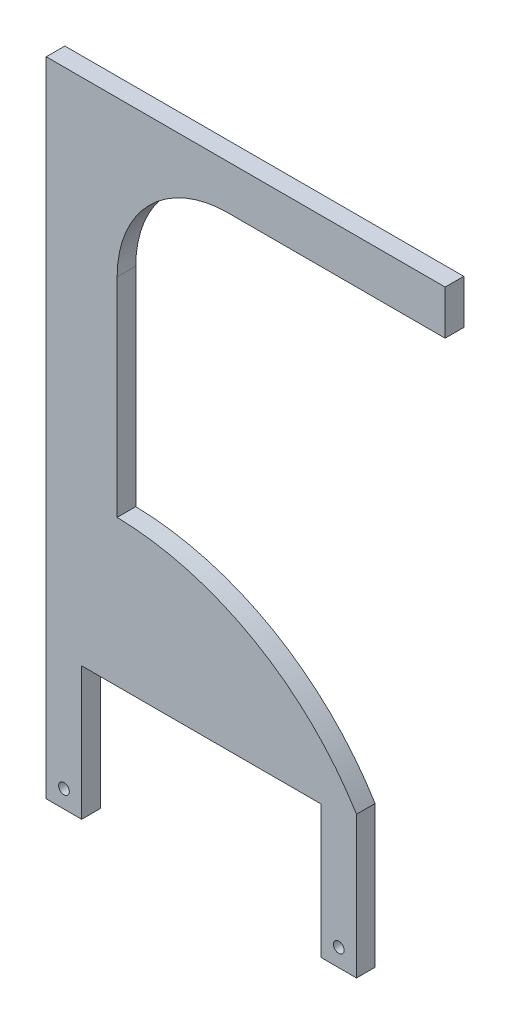
SolidWorks part; units mm, degrees
ref_plane "Plan de face" through (0, 0, 0) normal (0, 0, 1) x (1, 0, 0)
ref_plane "Plan de dessus" through (0, 0, 0) normal (0, 1, 0) x (1, 0, 0)
ref_plane "Plan de droite" through (0, 0, 0) normal (1, 0, 0) x (0, 0, -1)
sketch "Esquisse1" plane through (0, 0, 0) normal (0, 0, 1) x (1, 0, 0)
  line L41 (0, 145) -> (90, 145)
  line L42 (90, 145) -> (90, 135)
  line L43 (90, 135) -> (16, 135)
  line L44 (16, 135) -> (16, 63)
  line L46 (70, 32) -> (70, 0)
  line L47 (70, 0) -> (62, 0)
  line L50 (0, 0) -> (8, 0)
  line L51 (8, 0) -> (8, 30)
  line L55 (0, 0) -> (0, 145)
  line L56 (62, 0) -> (62, 30)
  line L57 (62, 30) -> (8, 30)
  arc A1 (16, 63) -> (70, 32) centre (14.5921, -1.9848) cw
  point P3 (16, 58.0837)
  dimension "D13" = 65
  dimension "D2" = 8
  dimension "D3" = 54
  dimension "D4" = 8
  dimension "D5" = 10
  dimension "D6" = 145
  dimension "D7" = 16
  dimension "D8" = 90
  dimension "D9" = 32
  dimension "D10" = 72
  dimension "D11" = 30
extrude "Boss.-Extru.1" add sketch "Esquisse1" along normal blind 4.2
sketch "Esquisse2" plane through (0, 0, 4.2) normal (0, 0, 1) x (1, 0, 0)
  line L0 (0, 0) -> (8, 0) construction
  line L1 (8, 0) -> (8, 30) construction
  line L2 (62, 0) -> (70, 0) construction
  line L3 (70, 0) -> (70, 32) construction
  circle A0 centre (4, 4) radius 1
  circle A1 centre (66, 4) radius 1
  dimension "D1" = 4
  dimension "D3" = 2
  dimension "D6" = 2
  dimension "D2" = 4
  dimension "D4" = 4
  dimension "D5" = 4
fillet "Congé1" [suppressed] radius 10
fillet "Congé2" radius 25 1 edges at (16, 135, 2.1)
sketch "Esquisse5" [suppressed] plane through (0, 0, 4.2) normal (0, 0, 1) x (1, 0, 0)
  line L0 (70, 80) -> (30, 80) construction
  line L1 (70, 80) -> (28.6377, 80)
  line L2 (70, 80) -> (70, 65)
  line L3 (70, 65) -> (28.6377, 65)
  line L4 (28.6377, 80) -> (28.6377, 65)
  line L5 (28.6377, 65) -> (28.6377, 105) construction
  line L6 (-8, 54) -> (0, 54) construction
  line L7 (-8, 80) -> (0, 80)
  line L8 (-8, 80) -> (-8, 54)
  line L9 (-8, 54) -> (0, 54)
  line L10 (0, 80) -> (0, 54)
  line L11 (0, 140) -> (0, 0) construction
  dimension "D2" = 15
extrude "Enlèv. mat.-Extru.1" [suppressed] cut sketch "Esquisse5" against normal up to surface (4.2 mm away) up to face at (40.9058, 64.3896, 0)
sketch "Esquisse6" plane through (0, 0, 4.2) normal (0, 0, 1) x (1, 0, 0)
  line L0 (41, 135) -> (90, 135) construction
  line L1 (90, 145) -> (82, 145)
  line L2 (90, 145) -> (90, 135)
  line L3 (90, 135) -> (82, 135)
  line L4 (82, 145) -> (82, 135)
  dimension "D1" = 8
extrude "Enlèv. mat.-Extru.2" [suppressed] cut sketch "Esquisse6" against normal up to surface (5 mm away) up to face at (40.9058, 64.3896, 0)
fillet "Congé3" [suppressed] radius 10
fillet "Congé4" [suppressed] radius 10
sketch "Esquisse7" [suppressed] plane through (0, 0, 4.2) normal (0, 0, 1) x (1, 0, 0)
  line L0 (0, 140) -> (0, 0) construction
  line L1 (100, 140) -> (0, 140)
  line L2 (100, 140) -> (100, 80)
  line L3 (100, 80) -> (0, 80)
  line L4 (0, 140) -> (0, 80)
  line L6 (0, 80) -> (-8, 80) construction
extrude "Enlèv. mat.-Extru.3" [suppressed] cut sketch "Esquisse7" against normal up to surface (5 mm away) up to face at (40.9058, 64.3896, 0)
sketch "Esquisse8" [suppressed] plane through (0, 0, 5) normal (0, 0, 1) x (1, 0, 0)
  line L5 (0, 80) -> (-15, 80)
  line L6 (-15, 80) -> (-15, 54)
  line L7 (-15, 54) -> (0, 54)
  line L8 (0, 80) -> (0, 0) construction
  line L9 (8, 54) -> (62, 54) construction
  line L10 (0, 80) -> (0, 54)
  line L18 (45, 80) -> (0, 80)
  line L19 (0, 80) -> (0, 0)
  line L20 (0, 0) -> (8, 0)
  line L21 (8, 0) -> (8, 54)
  line L22 (8, 54) -> (62, 54)
  line L23 (62, 54) -> (62, 0)
  line L24 (62, 0) -> (70, 0)
  line L25 (70, 0) -> (70, 60)
  line L26 (45, 80) -> (0, 80)
  line L27 (0, 54) -> (0, 0)
  line L28 (0, 0) -> (8, 0)
  line L29 (8, 0) -> (8, 54)
  line L30 (8, 54) -> (62, 54)
  line L31 (62, 54) -> (62, 0)
  line L32 (62, 0) -> (70, 0)
  line L33 (70, 0) -> (70, 60)
  arc A3 (70, 60) -> (61.2017, 69.9275) centre (60, 60) ccw
  arc A4 (53.7017, 74.9275) -> (61.2017, 69.9275) centre (62.4034, 79.8551) ccw
  arc A5 (53.7017, 74.9275) -> (45, 80) centre (45, 70) ccw
  arc A6 (70, 60) -> (61.2017, 69.9275) centre (60, 60) ccw
  arc A7 (53.7017, 74.9275) -> (61.2017, 69.9275) centre (62.4034, 79.8551) ccw
  arc A8 (53.7017, 74.9275) -> (45, 80) centre (45, 70) ccw
  dimension "D1" = 15
  dimension "D2" = 0
extrude "Enlèv. mat.-Extru.5" cut sketch "Esquisse2" against normal blind 10
hole_wizard "Dégagement M21" positions "Esquisse3" profile "Esquisse4" hole size "M2" standard "ISO" end condition through all
sketch "Esquisse3" plane through (0, 0, 4.2) normal (0, 0, 1) x (1, 0, 0)
  point P0 (4, 4)
  point P3 (66, 4)
sketch "Esquisse4" plane through (4, 4, 4.2) normal (1, 0, 0) x (0, -1, 0)
  line L0 (0, 0) -> (0, 4.2)
  line L1 (0, 4.2) -> (1.2, 4.2)
  line L2 (1.2, 4.2) -> (1.2, 0)
  line L5 (1.2, 0) -> (0, 0)
  line L11 (0, -6.35) -> (0, 107.95) construction
  dimension "Diamètre du perçage jusqu'au prochain" = 2.4
  dimension "Profondeur du perçage jusqu'au prochain" = 4.2
sketch "Esquisse9" plane through (0, 0, 4.2) normal (0, 0, 1) x (1, 0, 0)
  line L0 (90, 145) -> (0, 145) construction
  line L1 (90, 135) -> (65, 135)
  line L2 (90, 135) -> (90, 145)
  line L3 (90, 145) -> (65, 145)
  line L4 (65, 135) -> (65, 145)
  dimension "D1" = 25
extrude "Enlèv. mat.-Extru.6" [suppressed] cut sketch "Esquisse9" against normal up to surface (4.2 mm away) up to face at (5.2, 4, 0)
fillet "Congé5" [suppressed] radius 15
